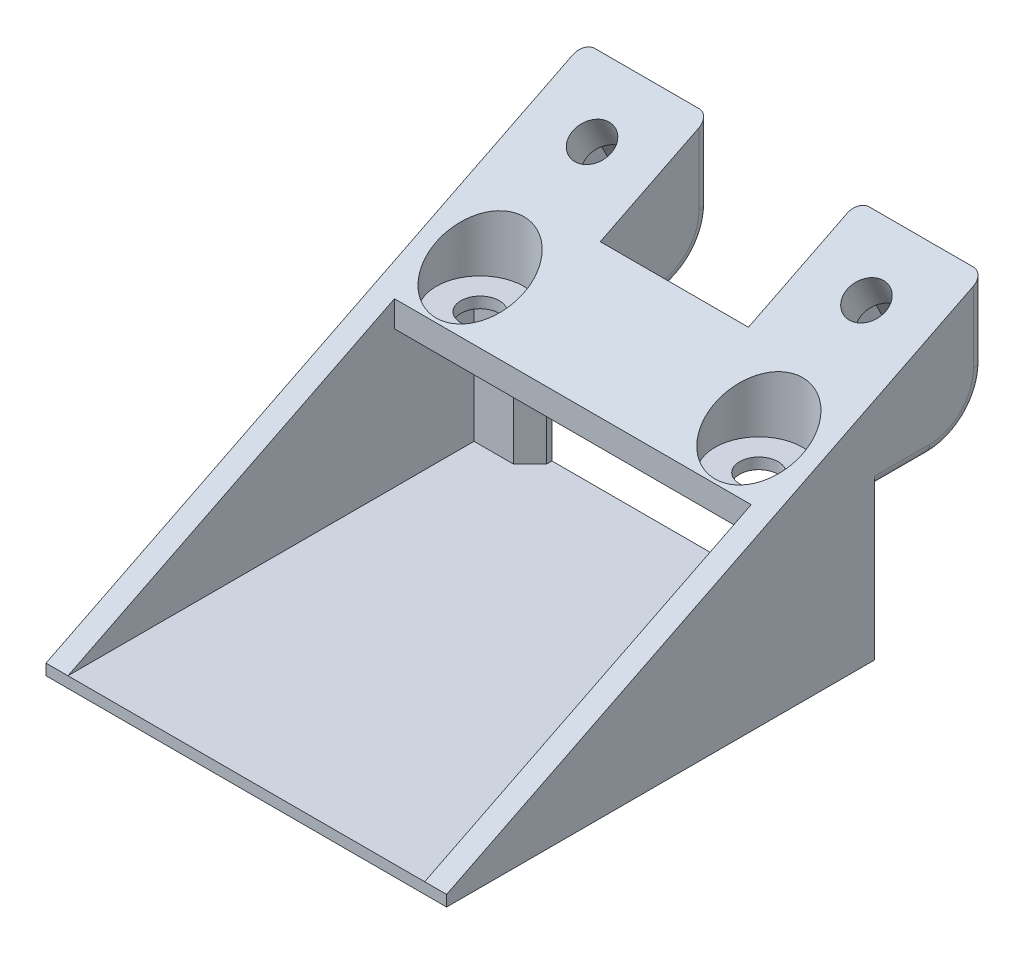
SolidWorks part; units mm, degrees
ref_plane "Front Plane" through (0, 0, 0) normal (0, 0, 1) x (1, 0, 0)
ref_plane "Top Plane" through (0, 0, 0) normal (0, 1, 0) x (1, 0, 0)
ref_plane "Right Plane" through (0, 0, 0) normal (1, 0, 0) x (0, 0, -1)
sketch "Sketch1" plane through (0, 0, 0) normal (1, 0, 0) x (0, 0, -1)
  line L0 (0, 19.5) -> (0, 0)
  line L1 (0, 0) -> (-38.9984, 0)
  line L2 (-38.9984, 0) -> (0, 19.5)
  dimension "D1" = 63.434
  dimension "D2" = 19.5
extrude "Boss-Extrude1" add sketch "Sketch1" along normal mid plane 32.5
sketch "Sketch10" plane through (0, 0, 0) normal (1, 0, 0) x (0, 0, -1)
  line L0 (-2, 0) -> (-2, 18.5)
  line L1 (-38.9984, 0) -> (0, 0) construction
  line L2 (0, 19.5) -> (-38.9984, 0) construction
  line L3 (-2, 18.5) -> (-38.9984, 0)
  line L4 (-38.9984, 0) -> (-2, 0)
  line L6 (0, 19.5) -> (-38.9984, 0)
  line L7 (-38.9984, 0) -> (0, 0)
  line L8 (0, 0) -> (0, 19.5)
  line L9 (0, 19.5) -> (-2, 18.5) construction
  line L10 (-2, 0) -> (0, 0) construction
  line L11 (0, 0) -> (0, 19.5) construction
  dimension "D1" = 0
  dimension "D2" = 2
extrude "Cut-Extrude7" cut sketch "Sketch10" against normal through all both and the other way through all
sketch "Sketch2" plane through (0, 0, 0) normal (0, 0, 1) x (1, 0, 0)
  line L0 (0, 1) -> (0, 11.5) construction
  line L3 (16.25, 19.5) -> (-16.25, 19.5) construction
  line L12 (-11.15, 12.5) -> (11.15, 12.5)
  line L13 (-11.15, 12.5) -> (-11.15, 0)
  line L14 (-11.15, 0) -> (11.15, 0)
  line L15 (11.15, 12.5) -> (11.15, 0)
  line L16 (-11.15, 12.5) -> (11.15, 0) construction
  line L17 (-11.15, 0) -> (11.15, 12.5) construction
  point P9 (0, 6.25)
  point P21 (0, 6.25)
  dimension "D1" = 22.3
  dimension "D2" = 12.5
  dimension "D3" = 7
extrude "Cut-Extrude1" cut sketch "Sketch2" along normal through all
sketch "Sketch6" plane through (-16.25, 0, 0) normal (1, 0, 0) x (0, 0, -1)
  line L0 (0, 0) -> (-38.9984, 0) construction
  line L1 (-38.9984, 0) -> (0, 19.5) construction
  line L2 (-2, 0) -> (-38.9984, 0)
  line L9 (-38.9984, 0) -> (-2, 18.5)
  line L16 (-2, 18.5) -> (-2, 0)
  line L17 (0, 19.5) -> (-2, 18.5)
  line L18 (0, 0) -> (0, 19.5)
  line L19 (-2, 0) -> (0, 0)
  line L21 (0, 19.5) -> (-2, 18.5)
  line L22 (0, 0) -> (0, 19.5)
  line L23 (-2, 0) -> (0, 0)
  dimension "D1" = 0
extrude "Boss-Extrude2" add sketch "Sketch6" against normal blind 2
mirror "Mirror1" about plane through (0, 0, 0) normal (1, 0, 0) of "Boss-Extrude2"
sketch "Sketch11" plane through (0, 0, 0) normal (1, 0, 0) x (0, 0, -1)
  line L0 (-2, 18.5) -> (-9.25, 14.8748)
  line L2 (-9.25, 12.5) -> (-2, 12.5)
  line L4 (-2, 12.5) -> (-2, 18.5)
  line L5 (-9.25, 12.5) -> (-9.25, 14.8748)
  line L7 (-2, 18.5) -> (-38.9984, 0) construction
  dimension "D1" = 7.25
extrude "Boss-Extrude4" add sketch "Sketch11" along normal up to surface and the other way up to surface up to face at (16.25, 6.1667, 14.3328) other way up to face at (-16.25, 6.1667, 14.3328)
sketch "Sketch12" plane through (0, 12.5, 0) normal (0, -1, 0) x (1, 0, 0)
  line L0 (0, 0) -> (0, 15.0811) construction
  line L3 (-11.15, 2) -> (-16.25, 2) construction
  circle A1 centre (-12.7, 5) radius 1.75
  circle A2 centre (12.7, 5) radius 1.75
  dimension "D1" = 3
  dimension "D2" = 3.5
  dimension "D4" = 25.4
extrude "Cut-Extrude8" cut sketch "Sketch12" against normal through all
sketch "Sketch14" plane through (0, 12.5, 0) normal (0, -1, 0) x (1, 0, 0)
  circle A2 centre (-12.7, 5) radius 4
  circle A3 centre (12.7, 5) radius 4
  dimension "D1" = 8
extrude "Cut-Extrude10" cut sketch "Sketch14" against normal through all from offset 1 offset against normal yes
sketch "Sketch15" plane through (0, 0, 0) normal (0, -1, 0) x (1, 0, 0)
  line L1 (-18.25, 38.9984) -> (18.25, 38.9984)
  line L2 (-18.25, 38.9984) -> (-18.25, 0)
  line L3 (-18.25, 0) -> (18.25, 0)
  line L4 (18.25, 38.9984) -> (18.25, 0)
extrude "Boss-Extrude5" add sketch "Sketch15" along normal blind 1
sketch "Sketch17" plane through (-18.25, 0, 0) normal (-1, 0, 0) x (0, 0, 1)
  line L0 (0, 19.5) -> (-10, 24.5002)
  line L1 (-10, 24.5002) -> (-10, 12.5)
  line L2 (-10, 12.5) -> (0, 12.5)
  line L3 (0, -1) -> (0, 19.5) construction
  line L4 (0, 12.5) -> (0, 19.5)
  line L5 (0, 19.5) -> (38.9984, 0) construction
  dimension "D1" = 10
extrude "Boss-Extrude6" add sketch "Sketch17" against normal up to surface (36.5 mm away) up to face at (18.25, 4.375, 19.4992)
sketch "Sketch18" plane through (0, 12.5, 0) normal (0, -1, 0) x (1, 0, 0)
  line L0 (-18.25, 0) -> (18.25, 0) construction
  line L1 (-6.75, 0) -> (6.75, 0)
  line L2 (-6.75, 0) -> (-6.75, -10)
  line L3 (-6.75, -10) -> (6.75, -10)
  line L4 (6.75, 0) -> (6.75, -10)
  line L5 (18.25, -10) -> (-18.25, -10) construction
  line L6 (0, 0) -> (0, -3.4177) construction
  line L7 (18.25, 0) -> (18.25, -10) construction
  dimension "D1" = 11.5
extrude "Cut-Extrude12" cut sketch "Sketch18" against normal through all
sketch "Sketch21" plane through (0, 15.5997, 7.8002) normal (0, 0.8944, 0.4472) x (1, 0, 0)
  line L0 (-6.75, 14.3112) -> (-12.5, 14.3112) construction
  line L1 (-6.75, 8.721) -> (-6.75, 19.9014) construction
  line L2 (0, 0) -> (0, 12.505) construction
  circle A0 centre (-12.5, 14.3112) radius 1.75
  circle A1 centre (12.5, 14.3112) radius 1.75
  dimension "D1" = 3.5
  dimension "D2" = 25
extrude "Cut-Extrude15" cut sketch "Sketch21" against normal through all
sketch "Sketch22" plane through (0, 15.5997, 7.8002) normal (0, 0.8944, 0.4472) x (1, 0, 0)
  line L1 (12.5, 18.0639) -> (9.25, 16.1876)
  line L2 (9.25, 16.1876) -> (9.25, 12.4348)
  line L3 (9.25, 12.4348) -> (12.5, 10.5584)
  line L4 (12.5, 10.5584) -> (15.75, 12.4348)
  line L5 (15.75, 12.4348) -> (15.75, 16.1876)
  line L6 (15.75, 16.1876) -> (12.5, 18.0639)
  line L7 (-12.5, 18.0639) -> (-15.75, 16.1876)
  line L8 (-15.75, 16.1876) -> (-15.75, 12.4348)
  line L9 (-15.75, 12.4348) -> (-12.5, 10.5584)
  line L10 (-12.5, 10.5584) -> (-9.25, 12.4348)
  line L11 (-9.25, 12.4348) -> (-9.25, 16.1876)
  line L12 (-9.25, 16.1876) -> (-12.5, 18.0639)
  circle A0 centre (12.5, 14.3112) radius 3.25 construction
  circle A1 centre (-12.5, 14.3112) radius 3.25 construction
  dimension "D1" = 6.5
extrude "Cut-Extrude16" cut sketch "Sketch22" against normal through all from offset 3 offset against normal yes
chamfer "Chamfer1" distance 1.5 angle 45 2 edges at (11.15, 6.25, 2) (-11.15, 6.25, 2)
fillet "Fillet1" radius 5 2 edges at (-8, 12.5, -10) (17, 12.5, -10)
fillet "Fillet2" radius 1 12 edges at (6.75, 12.5, -2.5) (6.75, 13.9645, -8.5355) (18.25, 12.5, -2.5) (18.25, 13.9645, -8.5355) (-18.25, 12.5, -2.5) (-18.25, 13.9645, -8.5355) (-6.75, 12.5, -2.5) (-6.75, 13.9645, -8.5355) (6.75, 21.0001, -10) (18.25, 21.0001, -10) (-18.25, 21.0001, -10) (-6.75, 21.0001, -10)
